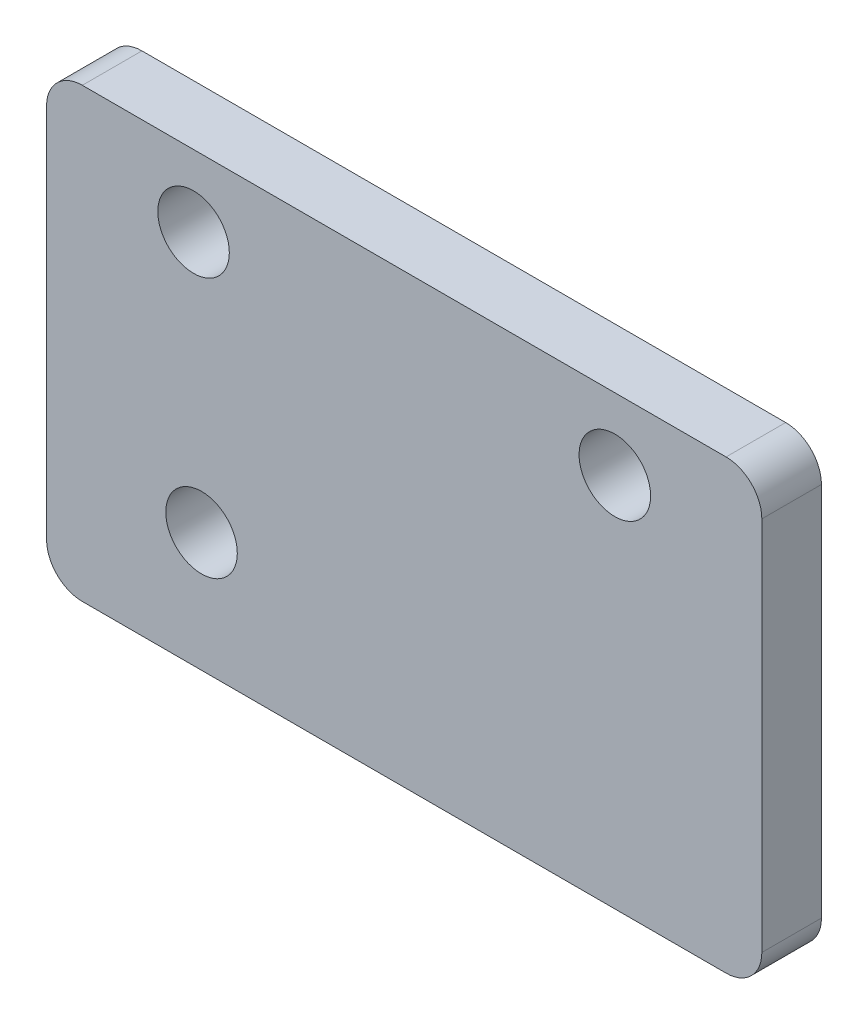
SolidWorks part; units mm, degrees
ref_plane "前视基准面" through (0, 0, 0) normal (0, 0, 1) x (1, 0, 0)
ref_plane "上视基准面" through (0, 0, 0) normal (0, 1, 0) x (1, 0, 0)
ref_plane "右视基准面" through (0, 0, 0) normal (1, 0, 0) x (0, 0, -1)
other "Configuration Table"
sketch "草图1" plane through (0, 0, 0) normal (0, 0, 1) x (1, 0, 0)
  line L0 (0, 0) -> (1.5, 0) construction
  line L2 (-15.5, 27.5) -> (38.5, 27.5)
  line L3 (-18.5, 24.5) -> (-18.5, -7)
  line L4 (-15.5, -10) -> (-8.825, -10)
  line L5 (41.5, 24.5) -> (41.5, -7)
  line L29 (33.3, -10) -> (38.5, -10)
  line L30 (31.175, -10) -> (-8.825, -10)
  line L34 (33.3, -10) -> (31.175, -10)
  arc A20 (38.5, 27.5) -> (41.5, 24.5) centre (38.5, 24.5) cw
  arc A21 (38.5, -10) -> (41.5, -7) centre (38.5, -7) ccw
  arc A22 (-18.5, -7) -> (-15.5, -10) centre (-15.5, -7) ccw
  arc A23 (-15.5, 27.5) -> (-18.5, 24.5) centre (-15.5, 24.5) ccw
  circle A32 centre (21.075, 0) radius 5.2518 construction
  dimension "D4" = 60
  dimension "D13" = 3
  dimension "D7" = 37.5
extrude "凸台-拉伸1" add sketch "草图1" along normal blind 5
sketch "草图2" plane through (0, 0, 5) normal (0, 0, 1) x (1, 0, 0)
  line L0 (21.075, 0) -> (21.075, 6.3806) construction
  line L1 (-15.5, 27.5) -> (38.5, 27.5) construction
  line L2 (11.5, 27.5) -> (11.5, 21.5) construction
  line L5 (29.17, 21.5) -> (-6.17, 21.5) construction
  circle A2 centre (-6.17, 21.5) radius 3
  circle A3 centre (29.17, 21.5) radius 3
  dimension "D1" = 6
  dimension "D5" = 6
  dimension "D3" = 35.34
extrude "切除-拉伸1" cut sketch "草图2" against normal blind 10 contours A2 | A3
sketch "草图4" plane through (0, 0, 5) normal (0, 0, 1) x (1, 0, 0)
  line L0 (41.5, 0) -> (21.5, 0) construction
  line L1 (41.5, 24.5) -> (41.5, -7) construction
  circle A0 centre (-5.5, 0) radius 3
  dimension "D3" = 6
  dimension "D2" = 27
extrude "切除-拉伸2" cut sketch "草图4" against normal blind 10 contours A0 | L0 | L0 region at (-5.5, 0, 5)
sketch "草图5" plane through (0, 0, -3) normal (0, 0, 1) x (1, 0, 0)
  circle A0 centre (-87.2851, 32.4678) radius 1.5
  dimension "D1" = 3
